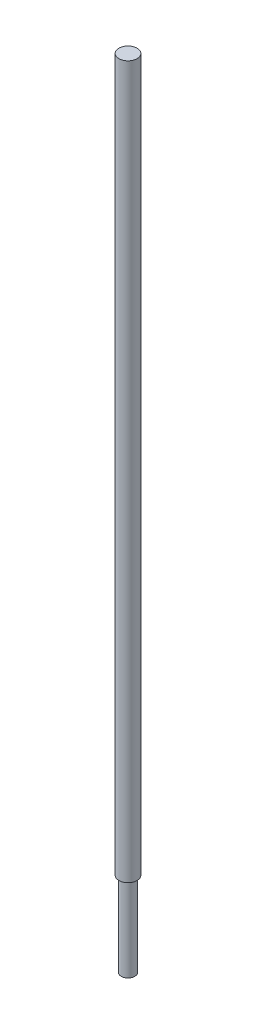
SolidWorks part; units mm, degrees
ref_plane "Ebene vorne" through (0, 0, 0) normal (0, 0, 1) x (1, 0, 0)
ref_plane "Ebene oben" through (0, 0, 0) normal (0, 1, 0) x (1, 0, 0)
ref_plane "Ebene rechts" through (0, 0, 0) normal (1, 0, 0) x (0, 0, -1)
sketch "Position" plane through (0, 0, 0) normal (0, 1, 0) x (1, 0, 0)
  circle A0 centre (14, 0) radius 1.5
  circle A1 centre (0, 0) radius 4.5
sketch "Length" plane through (0, 0, 0) normal (0, 0, 1) x (1, 0, 0)
  line L0 (0, 200) -> (0, 550)
  line L4 (14, 237) -> (14, 550)
sketch "Skizze3" plane through (0, 0, 0) normal (0, 1, 0) x (1, 0, 0)
  line L0 (-23.35, 0) -> (23.35, 0) construction
  circle A0 centre (0, 0) radius 4
extrude "Aufsatz-Linear austragen1" add sketch "Skizze3" along normal up to vertex (550 mm away) from vertex up to point (0, 550, 0) starting at point (0, 200, 0)
sketch "Skizze5" plane through (0, 200, 0) normal (0, -1, 0) x (1, 0, 0)
  circle A0 centre (0, 0) radius 4
  circle A1 centre (0, 0) radius 3
extrude "Schnitt-Linear austragen1" cut sketch "Skizze5" against normal up to vertex (37 mm away) up to point (14, 237, 0)
